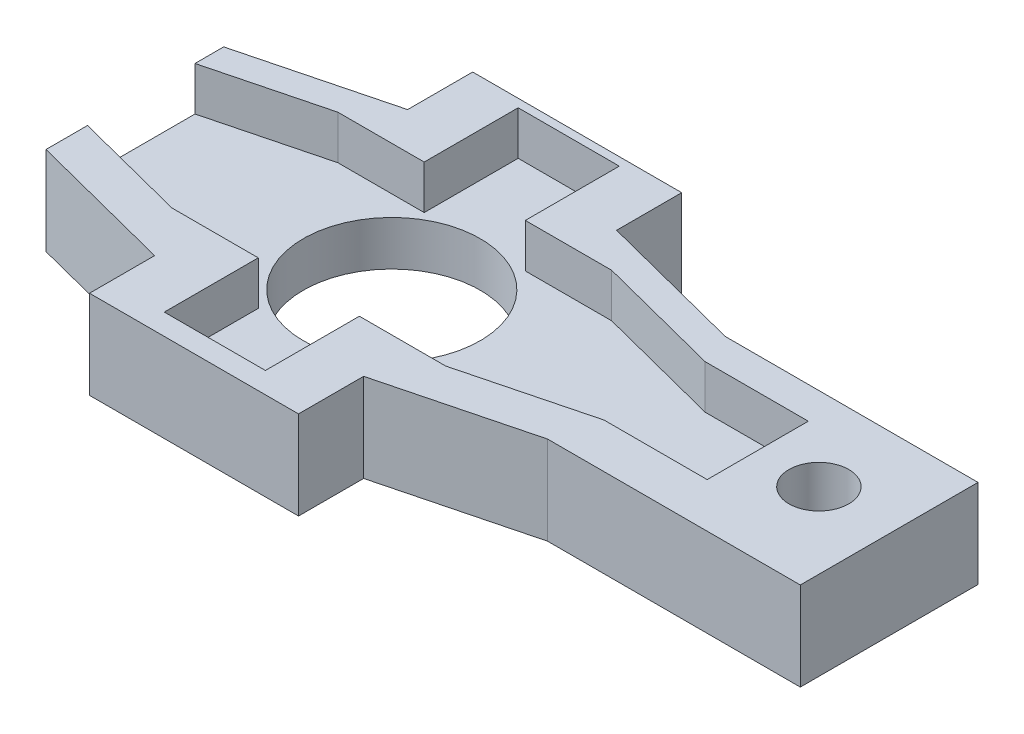
SolidWorks part; units mm, degrees
ref_plane "Front Plane" through (0, 0, 0) normal (0, 0, 1) x (1, 0, 0)
ref_plane "Top Plane" through (0, 0, 0) normal (0, 1, 0) x (1, 0, 0)
ref_plane "Right Plane" through (0, 0, 0) normal (1, 0, 0) x (0, 0, -1)
sketch "Sketch1" plane through (0, 0, 0) normal (0, 1, 0) x (1, 0, 0)
  line L0 (0, -0.2793) -> (0, 2.9072) construction
  line L6 (0, -0.2793) -> (1.7502, -0.2793) construction
  line L7 (0, 5.8463) -> (0, -0.2793) construction
  line L8 (6.5198, -0.2793) -> (0, -0.2793) construction
  line L16 (-4.7395, -3.1515) -> (4.7395, 2.5929) construction
  line L17 (-12.5989, -4.7429) -> (-12.5989, 4.1843)
  line L18 (-12.5989, 4.1843) -> (-5.1827, 6.0933)
  line L19 (-5.1827, 6.0933) -> (5.1827, 6.0933)
  line L20 (12.5989, 4.1843) -> (5.1827, 6.0933)
  line L21 (12.5989, 4.1843) -> (12.5989, -4.7429)
  line L22 (12.5989, -4.7429) -> (5.1827, -6.6518)
  line L23 (-5.1827, -6.6518) -> (5.1827, -6.6518)
  line L24 (-5.1827, -6.6518) -> (-12.5989, -4.7429)
  line L25 (-5.2505, -9.9052) -> (5.2505, -9.9052)
  line L26 (5.2505, -9.9052) -> (5.2505, 9.3466)
  line L27 (-5.2505, 9.3466) -> (5.2505, 9.3466)
  line L28 (-5.2505, -9.9052) -> (-5.2505, 9.3466)
  line L30 (12.5989, -4.7429) -> (25.2989, -4.7429)
  line L31 (12.5989, -4.7429) -> (12.5989, 4.1843)
  line L32 (12.5989, 4.1843) -> (25.2989, 4.1843)
  line L33 (25.2989, -4.7429) -> (25.2989, 4.1843)
  circle A0 centre (21.4889, 0) radius 1.5
  point P9 (15.7739, -0.9316)
  point P10 (21.7023, 0)
  dimension "D1" = 3
  dimension "D2" = 3.81
  dimension ".5" = 12.7
extrude "Boss-Extrude1" add sketch "Sketch1" along normal blind 4.445 contours L24 L28 L18 L17 | L28 L24 L23 L22 L26 L20 L19 L18 | L28 L25 L26 L22 L23 L24 | L26 L22 L21 L20 | L30 L33 L32 L21 A0 | L28 L18 L19 L20 L26 L27 region at (-8.7106, 0, 0.2793) region at (0, 0, 0.2793) region at (0, 0, 8.2784) region at (0, 0, -7.7199) region at (8.7106, 0, 0.2793) region at (18.78, 0, 0.2978)
sketch "Sketch2" plane through (0, 4.445, 0) normal (0, 1, 0) x (1, 0, 0)
  line L0 (-0.0115, 0.0428) -> (-0.0115, 4.6673) construction
  line L1 (-13.2161, -2.4972) -> (-13.2161, 2.5828)
  line L2 (-2.5515, -8.8472) -> (2.5285, -8.8472)
  line L3 (-2.5515, -8.8472) -> (-2.5515, 8.9328)
  line L4 (-2.5515, 8.9328) -> (2.5285, 8.9328)
  line L5 (2.5285, -8.8472) -> (2.5285, 8.9328)
  line L6 (-0.0115, 0.0428) -> (2.5285, 0.0428) construction
  line L7 (-0.0115, 8.9328) -> (-0.0115, 0.0428) construction
  line L8 (9.4506, 0.0428) -> (-0.0115, 0.0428) construction
  line L9 (13.1931, -2.4972) -> (6.8668, -4.1256)
  line L10 (13.1931, 2.5828) -> (6.8668, 4.2112)
  line L11 (-6.8898, -4.1256) -> (-13.2161, -2.4972)
  line L12 (-13.2161, 2.5828) -> (-6.8898, 4.2112)
  line L13 (-6.8898, -4.1256) -> (6.8668, -4.1256)
  line L14 (13.1931, 2.5828) -> (13.1931, -2.4972)
  line L15 (-6.8898, 4.2112) -> (6.8668, 4.2112)
  line L16 (-6.8898, -4.1256) -> (6.8668, 4.2112) construction
  line L17 (13.1931, 2.5828) -> (18.3743, 2.5828)
  line L18 (18.3743, 2.5828) -> (18.3743, -2.4972)
  line L19 (18.3743, -2.4972) -> (13.1931, -2.4972)
  circle A0 centre (-0.0115, 0.0428) radius 4.445
  line M26 (-12.5989, 4.1843) -> (-12.5989, -4.7429)
  dimension "D3" = 8.89
  dimension "D1" = 17.78
  dimension "D2" = 5.08
extrude "Cut-Extrude1" cut sketch "Sketch2" against normal blind 2.1996 contours A0 L3 L15 L12 L11 L13 M26 | L3 A0 | L13 A0 L5 L15 L3 | L5 A0 | A0 L5 L13 L9 L14 L10 L15 | A0 L13 L3 L2 L5 | A0 L13 L5 | L13 A0 | A0 L3 L13 | A0 L15 L3 | L15 A0 | A0 L5 L15 | A0 L15 L5 L4 L3 | L19 L18 L17 L14 region at (-7.8072, 4.445, -0.0428) region at (-0.0115, 4.445, 6.5415) region at (-2.2377, 4.445, 3.9606) region at (-2.2377, 4.445, -4.0462) region at (-0.0115, 4.445, -6.627) region at (-3.3295, 4.445, -0.0428) region at (-0.0115, 4.445, -0.0428) region at (-0.0115, 4.445, 4.2366) region at (-0.0115, 4.445, -4.3221) region at (2.2147, 4.445, 3.9606) region at (2.2147, 4.445, -4.0462) region at (8.0236, 4.445, -0.0428) region at (3.3065, 4.445, -0.0428) region at (15.7837, 4.445, -0.0428)
extrude "Cut-Extrude2" cut sketch "Sketch2<3>" against normal blind 19.9796 contours L13 A0 L5 L15 L3 | L5 A0 | L3 A0 | L15 A0 | L13 A0 region at (-3.3295, 4.445, -0.0428) region at (-0.0115, 4.445, -0.0428) region at (-0.0115, 4.445, 4.2366) region at (-0.0115, 4.445, -4.3221) region at (3.3065, 4.445, -0.0428)
sketch "Sketch2<3>" plane through (0, 4.445, 0) normal (0, 1, 0) x (1, 0, 0) same geometry as "Sketch2"
